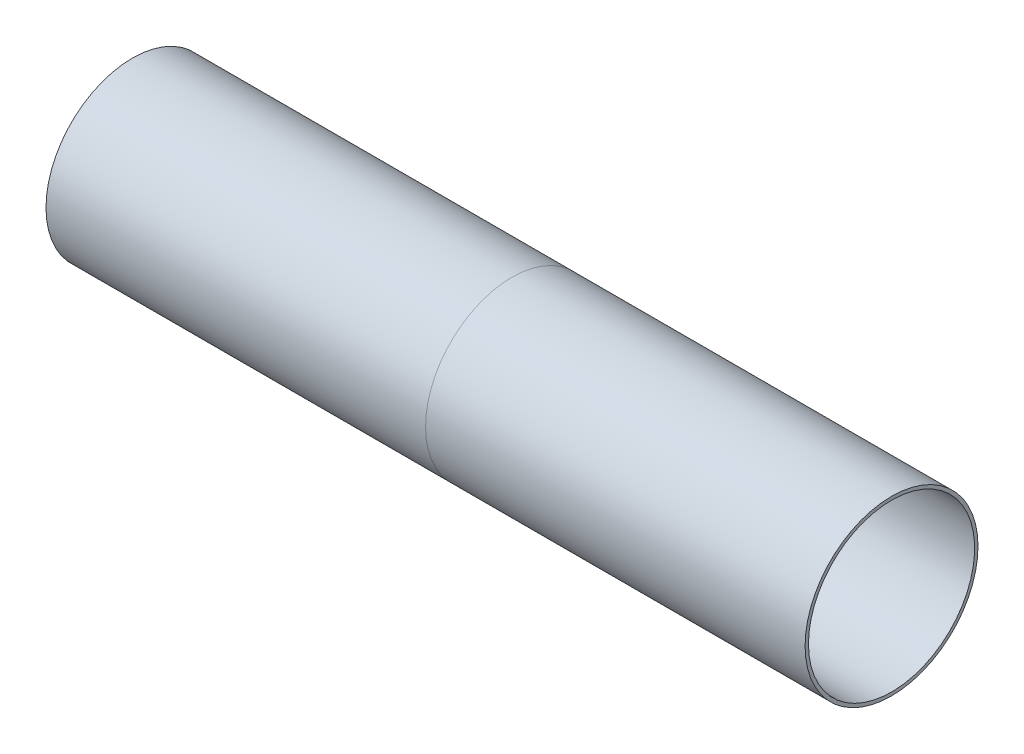
SolidWorks part; units mm, degrees
other "End Part"
other "Middle Bit"
other "Coupler"
ref_plane "Front Plane" through (0, 0, 0) normal (0, 0, 1) x (1, 0, 0)
ref_plane "Top Plane" through (0, 0, 0) normal (0, 1, 0) x (1, 0, 0)
ref_plane "Right Plane" through (0, 0, 0) normal (1, 0, 0) x (0, 0, -1)
sketch "Sketch2" plane through (0, 0, 0) normal (0, 1, 0) x (1, 0, 0)
  line L0 (0, 0) -> (180, 0)
  line L1 (180, 39.4) -> (180, 0) construction
  line L2 (0, 39.4) -> (0, 0) construction
  line L3 (180, 41) -> (0, 41)
  line L4 (180, 41) -> (180, 39.4)
  line L5 (180, 39.4) -> (0, 39.4)
  line L6 (0, 41) -> (0, 39.4)
  line L7 (90, 39.4) -> (90, 41) construction
  line L8 (180, 40.2) -> (0, 40.2) construction
  line L9 (0, 39.4) -> (11.4301, 38.4)
  line L10 (11.4301, 38.4) -> (12.4301, 39.4)
  line L11 (11.4301, 38.4) -> (11.4301, 39.4) construction
  line L12 (-12.4301, 39.4) -> (12.4301, 39.4)
  line L13 (0, 39.4) -> (-11.4301, 38.4)
  line L14 (-11.4301, 38.4) -> (-12.4301, 39.4)
  line L15 (-180, 39.4) -> (0, 39.4)
  line L16 (-180, 41) -> (0, 41)
  line L17 (-180, 41) -> (-180, 39.4)
  line L18 (-90, 41) -> (-90, 0) construction
  line L19 (-167.5699, 39.4) -> (-180, 39.4)
  line L20 (-168.5699, 38.4) -> (-167.5699, 39.4)
  line L21 (-180, 39.4) -> (-168.5699, 38.4)
  point P328 (90, 40.2)
  dimension "D1" = 180
  dimension "D2" = 41
  dimension "D3" = 1.6
  dimension "D4" = 45
  dimension "D5" = 5
  dimension "D6" = 1
revolve "Revolve1" add sketch "Sketch2" angle 360 about L0 region at (90, 0, -40.2) region at (7.9534, 0, -39.0667)
revolve "Revolve2" add sketch "Sketch2<3>" angle 360 about L0 region at (-90, 0, -40.2) region at (-7.9534, 0, -39.0667)
sketch "Sketch2<3>" plane through (0, 0, 0) normal (0, 1, 0) x (1, 0, 0) same geometry as "Sketch2"
sketch "Sketch3" plane through (0, 0, 0) normal (0, 1, 0) x (1, 0, 0)
  line L0 (-11.4301, 38.4) -> (0, 39.4)
  line L1 (0, 39.4) -> (11.4301, 38.4)
  line L2 (11.4301, 38.4) -> (11.4301, 37.2)
  line L3 (11.4301, 37.2) -> (-11.4301, 37.2)
  line L4 (-11.4301, 37.2) -> (-11.4301, 38.4)
  dimension "D1" = 1.2
revolve "Revolve3" add sketch "Sketch3" angle 360 about L0
